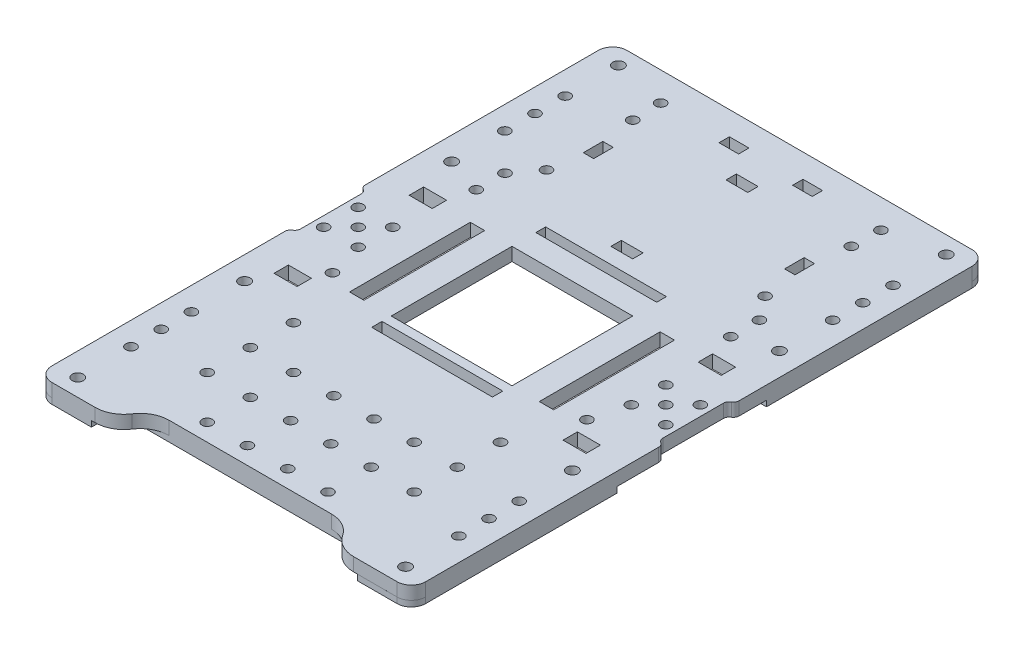
SolidWorks part; units mm, degrees
ref_plane "前视基准面" through (0, 0, 0) normal (0, 0, 1) x (1, 0, 0)
ref_plane "上视基准面" through (0, 0, 0) normal (0, 1, 0) x (1, 0, 0)
ref_plane "右视基准面" through (0, 0, 0) normal (1, 0, 0) x (0, 0, -1)
other "Configuration Table"
sketch "草图2" plane through (0, 0, 0) normal (0, 1, 0) x (1, 0, 0)
  line L0 (-65, 0) -> (65, 0) construction
  line L1 (-65, 100) -> (65, 100)
  line L2 (-65, 100) -> (-65, -100)
  line L3 (-65, -100) -> (65, -100)
  line L4 (65, 100) -> (65, -100)
  line L5 (-65, 100) -> (65, -100) construction
  line L6 (-65, -100) -> (65, 100) construction
  line L7 (65, 0) -> (63, 0) construction
  line L8 (63, 0) -> (59.5, 0) construction
  line L9 (59.5, 0) -> (47.5, 0) construction
  line L10 (47.5, 0) -> (53.5, 0) construction
  line L11 (53.5, 0) -> (53.5, 6) construction
  line L12 (53.5, 6) -> (53.5, -6) construction
  line L13 (53.5, -6) -> (47.5, -6) construction
  line L14 (47.5, -6) -> (47.5, 6) construction
  line L15 (47.5, 6) -> (59.5, 6) construction
  line L16 (59.5, 6) -> (59.5, -6) construction
  line L17 (-65, 0) -> (-63, 0) construction
  line L18 (-63, 0) -> (-59.5, 0) construction
  line L19 (-59.5, 0) -> (-47.5, 0) construction
  line L20 (-47.5, 0) -> (-53.5, 0) construction
  line L21 (-53.5, 0) -> (-53.5, 6) construction
  line L22 (-53.5, 6) -> (-53.5, -6) construction
  line L23 (-53.5, -6) -> (-59.5, -6) construction
  line L24 (-59.5, -6) -> (-59.5, 6) construction
  line L25 (-59.5, 6) -> (-47.5, 6) construction
  line L26 (-47.5, 6) -> (-47.5, -6) construction
  circle A0 centre (-59.5, 6) radius 1.8
  circle A1 centre (-47.5, 6) radius 1.8
  circle A2 centre (-59.5, -6) radius 1.8
  circle A3 centre (-47.5, -6) radius 1.8
  circle A4 centre (-53.5, 0) radius 1.8
  circle A5 centre (53.5, 0) radius 1.8
  circle A6 centre (59.5, 6) radius 1.8
  circle A7 centre (59.5, -6) radius 1.8
  circle A8 centre (47.5, -6) radius 1.8
  circle A9 centre (47.5, 6) radius 1.8
  point P0 (0, 0)
  dimension "D13" = 3.6
  dimension "D14" = 3.6
  dimension "D15" = 3.6
  dimension "D16" = 3.6
  dimension "D17" = 3.6
  dimension "D18" = 3.6
  dimension "D19" = 3.6
  dimension "D20" = 3.6
  dimension "D21" = 3.6
  dimension "D22" = 3.6
  dimension "D1" = 200
  dimension "D2" = 130
  dimension "D3" = 2
  dimension "D4" = 3.5
  dimension "D5" = 12
  dimension "D6" = 6
  dimension "D7" = 12
  dimension "D8" = 2
  dimension "D9" = 3.5
  dimension "D10" = 12
  dimension "D11" = 6
  dimension "D12" = 12
extrude "凸台-拉伸1" add sketch "草图2" along normal blind 4.6
fillet "圆角1" radius 5 4 edges at (-65, 2.3, -100) (65, 2.3, -100) (-65, 2.3, 100) (65, 2.3, 100)
sketch "草图3" plane through (0, 4.6, 0) normal (0, 1, 0) x (1, 0, 0)
  line L0 (-65, 0) -> (65, 0) construction
  line L1 (-65, 95) -> (-65, -95) construction
  line L2 (65, -95) -> (65, 95) construction
  line L4 (-63, 12) -> (-67, 12)
  line L5 (-63, 12) -> (-63, -12)
  line L6 (-63, -12) -> (-67, -12)
  line L7 (-67, 12) -> (-67, -12)
  line L8 (-63, 12) -> (-67, -12) construction
  line L9 (-63, -12) -> (-67, 12) construction
  line L10 (63, 12) -> (67, 12)
  line L11 (63, 12) -> (63, -12)
  line L12 (63, -12) -> (67, -12)
  line L13 (67, 12) -> (67, -12)
  line L14 (63, 12) -> (67, -12) construction
  line L15 (63, -12) -> (67, 12) construction
  dimension "D1" = 24
  dimension "D2" = 4
  dimension "D3" = 24
  dimension "D4" = 4
extrude "切除-拉伸1" cut sketch "草图3" against normal blind 4.6
fillet "圆角2" radius 2 4 edges at (65, 2.3, 12) (65, 2.3, -12) (-65, 2.3, 12) (-65, 2.3, -12)
fillet "圆角3" radius 2 4 edges at (-63, 2.3, 12) (-63, 2.3, -12) (63, 2.3, 12) (63, 2.3, -12)
sketch "草图4" plane through (0, 0, 0) normal (0, 1, 0) x (1, 0, 0)
  line L0 (65, 14) -> (57, 14) construction
  line L1 (57, 14) -> (57, 120) construction
  line L2 (65, -14) -> (57, -14) construction
  line L3 (65, -95) -> (65, -14) construction
  line L4 (57, -14) -> (57, -94) construction
  line L5 (57, -94) -> (57, -65) construction
  line L6 (57, -65) -> (57, -54) construction
  line L7 (-65, -94) -> (-57, -94) construction
  line L8 (-65, -14) -> (-65, -95) construction
  line L9 (-57, -94) -> (-57, -65) construction
  line L10 (-57, -65) -> (-57, -54.5) construction
  line L11 (-57, -54.5) -> (-57, -65) construction
  line L12 (-57, -65) -> (-57, -36) construction
  line L13 (57, -65) -> (57, -36) construction
  line L14 (57, 14) -> (57, 36) construction
  line L15 (57, 36) -> (57, 65) construction
  line L16 (57, 65) -> (57, 75.5) construction
  line L17 (57, 75.5) -> (57, 54.5) construction
  line L18 (57, 65) -> (57, 94) construction
  line L19 (-65, 14) -> (-57, 14) construction
  line L20 (-57, 14) -> (-57, 36) construction
  line L21 (-57, 36) -> (-57, 54.5) construction
  line L22 (-57, 54.5) -> (-57, 65) construction
  line L23 (-57, 65) -> (-57, 75.5) construction
  line L24 (-57, 75.5) -> (-57, 94) construction
  line L25 (-57, -65) -> (-57, -75.5) construction
  line L26 (-57, -75.5) -> (57, -75.5) construction
  line L27 (57, -65) -> (57, -54.5) construction
  arc A0 (65, -14) -> (64, -12.2679) centre (63, -14) ccw construction
  circle A1 centre (57, 65) radius 1.8
  circle A2 centre (57, 75.5) radius 1.8
  circle A3 centre (57, 54.5) radius 1.8
  circle A4 centre (57, 94) radius 1.95
  circle A5 centre (57, 36) radius 1.95
  circle A6 centre (-57, 94) radius 1.95
  circle A7 centre (-57, 75.5) radius 1.8
  circle A8 centre (-57, 65) radius 1.8
  circle A9 centre (-57, 54.5) radius 1.8
  circle A10 centre (-57, 36) radius 1.95
  circle A11 centre (-57, -36) radius 1.95
  circle A12 centre (-57, -65) radius 1.8
  circle A13 centre (-57, -54.5) radius 1.8
  circle A14 centre (-57, -75.5) radius 1.8
  circle A15 centre (-57, -94) radius 1.95
  circle A16 centre (57, -65) radius 1.8
  circle A18 centre (57, -75.5) radius 1.8
  circle A19 centre (57, -54.5) radius 1.8
  circle A20 centre (57, -36) radius 1.95
  circle A21 centre (57, -94) radius 1.95
  dimension "D15" = 3.6
  dimension "D16" = 3.6
  dimension "D17" = 3.6
  dimension "D18" = 3.9
  dimension "D19" = 3.9
  dimension "D20" = 3.9
  dimension "D21" = 3.6
  dimension "D22" = 3.6
  dimension "D23" = 3.6
  dimension "D24" = 3.9
  dimension "D25" = 3.9
  dimension "D26" = 3.6
  dimension "D27" = 3.6
  dimension "D29" = 3.6
  dimension "D30" = 3.9
  dimension "D31" = 3.6
  dimension "D32" = 10.5
  dimension "D33" = 3.6
  dimension "D34" = 3.6
  dimension "D35" = 3.9
  dimension "D36" = 3.9
  dimension "D1" = 8
  dimension "D2" = 106
  dimension "D3" = 8
  dimension "D4" = 80
  dimension "D5" = 29
  dimension "D6" = 11
  dimension "D7" = 8
  dimension "D8" = 29
  dimension "D9" = 22
  dimension "D10" = 29
  dimension "D11" = 10.5
  dimension "D12" = 21
  dimension "D13" = 29
  dimension "D14" = 8
  dimension "D28" = 10.5
extrude "切除-拉伸2" cut sketch "草图4" along normal blind 4.6
sketch "草图5" plane through (0, 4.6, 0) normal (0, 1, 0) x (1, 0, 0)
  line L0 (0, 100) -> (38.3, 100) construction
  line L1 (60, 100) -> (-60, 100) construction
  line L2 (38.3, 100) -> (-38.3, 100) construction
  line L3 (-38.3, 100) -> (-38.3, 90) construction
  line L4 (-38.3, 90) -> (-12.8, 90) construction
  line L5 (38.3, 100) -> (38.3, 90) construction
  line L6 (38.3, 90) -> (12.8, 90) construction
  line L7 (0, 21) -> (0, 31) construction
  line L8 (-16.2, 91.8) -> (-9.4, 91.8)
  line L9 (-16.2, 91.8) -> (-16.2, 88.2)
  line L10 (-16.2, 88.2) -> (-9.4, 88.2)
  line L11 (-9.4, 91.8) -> (-9.4, 88.2)
  line L12 (-16.2, 91.8) -> (-9.4, 88.2) construction
  line L13 (-16.2, 88.2) -> (-9.4, 91.8) construction
  line L14 (9.4, 91.8) -> (16.2, 91.8)
  line L15 (9.4, 91.8) -> (9.4, 88.2)
  line L16 (9.4, 88.2) -> (16.2, 88.2)
  line L17 (16.2, 91.8) -> (16.2, 88.2)
  line L18 (9.4, 91.8) -> (16.2, 88.2) construction
  line L19 (9.4, 88.2) -> (16.2, 91.8) construction
  line L20 (-21, 21) -> (21, 21)
  line L21 (-21, 21) -> (-21, -21)
  line L22 (-21, -21) -> (21, -21)
  line L23 (21, 21) -> (21, -21)
  line L24 (-21, 21) -> (21, -21) construction
  line L25 (-21, -21) -> (21, 21) construction
  line L26 (0, 31) -> (0, -21) construction
  line L27 (0, -21) -> (0, -31) construction
  line L28 (-60, -100) -> (60, -100) construction
  line L29 (-21, 32.7) -> (21, 32.7)
  line L30 (-21, 32.7) -> (-21, 29.3)
  line L31 (-21, 29.3) -> (21, 29.3)
  line L32 (21, 32.7) -> (21, 29.3)
  line L33 (-21, 32.7) -> (21, 29.3) construction
  line L34 (-21, 29.3) -> (21, 32.7) construction
  line L35 (-21, -29.3) -> (21, -29.3)
  line L36 (-21, -29.3) -> (-21, -32.7)
  line L37 (-21, -32.7) -> (21, -32.7)
  line L38 (21, -29.3) -> (21, -32.7)
  line L39 (-21, -29.3) -> (21, -32.7) construction
  line L40 (-21, -32.7) -> (21, -29.3) construction
  line L41 (-35, -91) -> (35, -91)
  line L42 (-35, -91) -> (-35, -109)
  line L43 (-35, -109) -> (35, -109)
  line L44 (35, -91) -> (35, -109)
  line L45 (-35, -91) -> (35, -109) construction
  line L46 (-35, -109) -> (35, -91) construction
  circle A0 centre (38.3, 90) radius 1.8
  circle A1 centre (-38.3, 90) radius 1.8
  point P19 (0, 0)
  point P37 (0, -100)
  dimension "D7" = 3.6
  dimension "D8" = 3.6
  dimension "D1" = 38.3
  dimension "D2" = 76.6
  dimension "D3" = 10
  dimension "D4" = 25.5
  dimension "D5" = 10
  dimension "D6" = 25.5
  dimension "D9" = 3.6
  dimension "D10" = 6.8
  dimension "D11" = 3.6
  dimension "D12" = 6.8
  dimension "D13" = 42
  dimension "D14" = 10
  dimension "D15" = 10
  dimension "D16" = 3.4
  dimension "D17" = 42
  dimension "D18" = 3.4
  dimension "D19" = 42
  dimension "D20" = 18
  dimension "D21" = 70
extrude "切除-拉伸3" cut sketch "草图5" against normal blind 4.6
fillet "圆角4" radius 10 2 edges at (-35, 2.3, 100) (35, 2.3, 100)
fillet "圆角5" radius 10 2 edges at (-35, 2.3, 91) (35, 2.3, 91)
sketch "草图6" plane through (0, 4.6, 0) normal (0, 1, 0) x (1, 0, 0)
  line L0 (0, -91) -> (0, -85) construction
  line L1 (28.2466, -91) -> (-28.2466, -91) construction
  line L2 (0, -85) -> (-7, -85) construction
  line L3 (-7, -85) -> (7, -85) construction
  line L4 (7, -85) -> (21, -85) construction
  line L5 (21, -85) -> (21, -70) construction
  line L6 (21, -70) -> (21, -55) construction
  line L7 (21, -55) -> (7, -55) construction
  line L8 (7, -55) -> (-7, -55) construction
  line L9 (-7, -55) -> (-21, -55) construction
  line L10 (-21, -55) -> (-35, -55) construction
  line L11 (-35, -55) -> (-35, -70) construction
  line L12 (-35, -70) -> (-35, -85) construction
  line L13 (-35, -85) -> (-21, -85) construction
  line L14 (21, -85) -> (35, -85) construction
  line L15 (35, -85) -> (35, -70) construction
  line L16 (35, -70) -> (35, -55) construction
  line L17 (35, -55) -> (35, -40) construction
  line L18 (35, -40) -> (21, -40) construction
  line L19 (21, -40) -> (7, -40) construction
  line L20 (7, -40) -> (-7, -40) construction
  line L21 (-7, -40) -> (-21, -40) construction
  line L22 (-21, -40) -> (-35, -40) construction
  line L23 (-35, -40) -> (-35, -70) construction
  line L24 (-35, -70) -> (-21, -70) construction
  line L25 (-21, -70) -> (-7, -70) construction
  line L26 (-7, -70) -> (7, -70) construction
  line L27 (21, -70) -> (36, -70) construction
  line L28 (36, -70) -> (36, -55) construction
  line L29 (36, -55) -> (36, -40) construction
  line L30 (-21, -70) -> (-36, -70) construction
  line L31 (-36, -70) -> (-36, -55) construction
  line L32 (-36, -55) -> (-36, -40) construction
  circle A0 centre (-7, -85) radius 1.8
  circle A1 centre (-21, -85) radius 1.8
  circle A2 centre (7, -85) radius 1.8
  circle A3 centre (21, -85) radius 1.8
  circle A4 centre (21, -70) radius 1.8
  circle A5 centre (7, -70) radius 1.8
  circle A6 centre (-7, -70) radius 1.8
  circle A7 centre (-21, -70) radius 1.8
  circle A8 centre (-21, -55) radius 1.8
  circle A9 centre (-7, -55) radius 1.8
  circle A10 centre (7, -55) radius 1.8
  circle A11 centre (21, -55) radius 1.8
  circle A12 centre (36, -70) radius 1.8
  circle A13 centre (36, -55) radius 1.8
  circle A14 centre (36, -40) radius 1.8
  circle A15 centre (-36, -40) radius 1.8
  circle A16 centre (-36, -55) radius 1.8
  circle A17 centre (-36, -70) radius 1.8
  dimension "D15" = 3.6
  dimension "D16" = 3.6
  dimension "D17" = 3.6
  dimension "D18" = 3.6
  dimension "D19" = 3.6
  dimension "D20" = 3.6
  dimension "D21" = 3.6
  dimension "D22" = 3.6
  dimension "D23" = 3.6
  dimension "D24" = 3.6
  dimension "D25" = 3.6
  dimension "D26" = 3.6
  dimension "D27" = 15
  dimension "D33" = 3.6
  dimension "D34" = 3.6
  dimension "D35" = 3.6
  dimension "D36" = 3.6
  dimension "D37" = 3.6
  dimension "D38" = 3.6
  dimension "D1" = 6
  dimension "D2" = 7
  dimension "D3" = 14
  dimension "D4" = 14
  dimension "D5" = 15
  dimension "D6" = 15
  dimension "D7" = 14
  dimension "D8" = 14
  dimension "D9" = 14
  dimension "D10" = 14
  dimension "D11" = 15
  dimension "D12" = 14
  dimension "D13" = 14
  dimension "D14" = 15
  dimension "D28" = 15
  dimension "D29" = 15
  dimension "D30" = 15
  dimension "D31" = 15
  dimension "D32" = 15
extrude "切除-拉伸4" cut sketch "草图6" against normal blind 4.6
sketch "草图7" plane through (0, 4.6, 0) normal (0, 1, 0) x (1, 0, 0)
  line L0 (0, 100) -> (38, 100) construction
  line L1 (60, 100) -> (-60, 100) construction
  line L2 (38, 100) -> (-38, 100) construction
  line L3 (-38, 100) -> (-38, 80) construction
  line L4 (-38, 80) -> (-38, 50) construction
  line L5 (-38, 50) -> (38, 50) construction
  line L6 (38, 50) -> (38, 80) construction
  circle A0 centre (-38, 80) radius 1.8
  circle A1 centre (38, 80) radius 1.8
  circle A2 centre (38, 50) radius 1.8
  circle A3 centre (-38, 50) radius 1.8
  dimension "D7" = 3.6
  dimension "D8" = 3.6
  dimension "D9" = 3.6
  dimension "D10" = 3.6
  dimension "D1" = 38
  dimension "D2" = 76
  dimension "D3" = 20
  dimension "D4" = 30
  dimension "D5" = 76
  dimension "D6" = 30
extrude "切除-拉伸5" cut sketch "草图7" against normal blind 4.6
sketch "草图8" plane through (0, 4.6, 0) normal (0, 1, 0) x (1, 0, 0)
  line L0 (-38, 80) -> (38, 50) construction
  line L1 (38, 50) -> (0, 65) construction
  line L2 (0, 65) -> (-35, 65) construction
  line L3 (-35, 65) -> (35, 65) construction
  line L4 (35, 65) -> (0, 65) construction
  line L5 (0, 65) -> (0, 80) construction
  line L6 (0, 80) -> (0, 40) construction
  line L8 (-3.7805, 81.7985) -> (3.7805, 81.7985)
  line L9 (-3.7805, 81.7985) -> (-3.7805, 78.2015)
  line L10 (-3.7805, 78.2015) -> (3.7805, 78.2015)
  line L11 (3.7805, 81.7985) -> (3.7805, 78.2015)
  line L12 (-3.7805, 81.7985) -> (3.7805, 78.2015) construction
  line L13 (-3.7805, 78.2015) -> (3.7805, 81.7985) construction
  line L14 (-3.7805, 38.1892) -> (3.7805, 38.1892)
  line L15 (-3.7805, 38.1892) -> (-3.7805, 41.8108)
  line L16 (-3.7805, 41.8108) -> (3.7805, 41.8108)
  line L17 (3.7805, 38.1892) -> (3.7805, 41.8108)
  line L18 (-3.7805, 38.1892) -> (3.7805, 41.8108) construction
  line L19 (-3.7805, 41.8108) -> (3.7805, 38.1892) construction
  line L20 (33.2, 68.4) -> (36.8, 68.4)
  line L21 (33.2, 68.4) -> (33.2, 61.6)
  line L22 (33.2, 61.6) -> (36.8, 61.6)
  line L23 (36.8, 68.4) -> (36.8, 61.6)
  line L24 (33.2, 68.4) -> (36.8, 61.6) construction
  line L25 (33.2, 61.6) -> (36.8, 68.4) construction
  line L26 (-36.8, 68.4) -> (-33.2, 68.4)
  line L27 (-36.8, 68.4) -> (-36.8, 61.6)
  line L28 (-36.8, 61.6) -> (-33.2, 61.6)
  line L29 (-33.2, 68.4) -> (-33.2, 61.6)
  line L30 (-36.8, 68.4) -> (-33.2, 61.6) construction
  line L31 (-36.8, 61.6) -> (-33.2, 68.4) construction
  dimension "D1" = 35
  dimension "D2" = 70
  dimension "D3" = 40
  dimension "D4" = 6.8
  dimension "D5" = 3.6
  dimension "D6" = 6.8
  dimension "D7" = 3.6
extrude "切除-拉伸6" cut sketch "草图8" against normal blind 4.6
sketch "草图10" plane through (0, 4.6, 0) normal (0, 1, 0) x (1, 0, 0)
  line L0 (0, 0) -> (44.25, 0) construction
  line L1 (44.25, 0) -> (-44.25, 0) construction
  line L2 (36, -38.2) -> (73.5514, -38.2) construction
  line L3 (73.5514, -38.2) -> (-76.1567, -38.2) construction
  line L4 (44.25, 0) -> (44.25, -38.2) construction
  line L5 (44.25, -38.2) -> (44.25, -18.2) construction
  line L6 (-44.25, 0) -> (-44.25, -38.2) construction
  line L7 (-44.25, -38.2) -> (-44.25, -18.1899) construction
  line L8 (-44.25, -18.1899) -> (-43.1477, 41.8) construction
  line L9 (-43.1477, 41.8) -> (44.25, 41.8) construction
  line L10 (0, 38.1892) -> (-44.25, 38.1892) construction
  line L11 (-3.7805, 38.1892) -> (3.7805, 38.1892) construction
  line L12 (-44.25, 38.1892) -> (44.25, 38.1892) construction
  line L13 (-44.25, -18.1899) -> (-44.25, 41.8101) construction
  line L14 (44.25, -18.2) -> (44.25, 41.8) construction
  line L15 (44.25, -18.2) -> (44.25, -8.2) construction
  line L16 (-44.25, -18.1899) -> (-44.25, -8.1899) construction
  line L17 (-44.25, -18.1899) -> (-44.25, 31.8101) construction
  line L18 (-44.25, 31.8101) -> (44.25, 31.8101) construction
  circle A0 centre (36, -40) radius 1.8 construction
  circle A1 centre (44.25, 41.8) radius 1.8
  circle A2 centre (-44.25, 41.8101) radius 1.8
  circle A3 centre (-44.25, -18.1899) radius 1.8
  circle A4 centre (44.25, -18.2) radius 1.8
  circle A5 centre (-44.25, 31.8101) radius 1.8
  circle A6 centre (44.25, 31.8101) radius 1.8
  dimension "D9" = 3.6
  dimension "D10" = 3.6
  dimension "D11" = 3.6
  dimension "D12" = 3.6
  dimension "D16" = 3.6
  dimension "D17" = 3.6
  dimension "D1" = 44.25
  dimension "D2" = 88.5
  dimension "D3" = 20
  dimension "D4" = 60
  dimension "D5" = 44.25
  dimension "D6" = 88.5
  dimension "D7" = 60
  dimension "D8" = 60
  dimension "D13" = 10
  dimension "D14" = 10
  dimension "D15" = 50
extrude "切除-拉伸8" cut sketch "草图10" against normal blind 4.6
sketch "草图9" plane through (0, 4.6, 0) normal (0, 1, 0) x (1, 0, 0)
  line L0 (21, 0) -> (33, 0) construction
  line L1 (21, -21) -> (21, 21) construction
  line L2 (-21, 0) -> (-33, 0) construction
  line L3 (-21, 21) -> (-21, -21) construction
  line L4 (35.5, -21) -> (65, -21) construction
  line L9 (30.5, 21) -> (35.5, -21) construction
  line L10 (30.5, -21) -> (35.5, 21) construction
  line L15 (-35.5, 21) -> (-30.5, -21) construction
  line L16 (-35.5, -21) -> (-30.5, 21) construction
  line L17 (65, -95) -> (65, -14) construction
  line L18 (-35.5, -21) -> (-65, -21) construction
  line L23 (46.25, -18.5) -> (54.25, -23.5) construction
  line L24 (46.25, -23.5) -> (54.25, -18.5) construction
  line L25 (-65, -14) -> (-65, -95) construction
  line L26 (-35.5, 21) -> (-65, 21) construction
  line L31 (-54.25, -18.5) -> (-46.25, -23.5) construction
  line L32 (-54.25, -23.5) -> (-46.25, -18.5) construction
  line L33 (-65, 95) -> (-65, 14) construction
  line L34 (35.5, 21) -> (65, 21) construction
  line L35 (-54.25, 23.5) -> (-46.25, 23.5)
  line L36 (-54.25, 23.5) -> (-54.25, 18.5)
  line L37 (-54.25, 18.5) -> (-46.25, 18.5)
  line L38 (-46.25, 23.5) -> (-46.25, 18.5)
  line L39 (-54.25, 23.5) -> (-46.25, 18.5) construction
  line L40 (-54.25, 18.5) -> (-46.25, 23.5) construction
  line L41 (65, 14) -> (65, 95) construction
  line L42 (50.25, -21) -> (50.25, -31) construction
  line L43 (46.25, 23.5) -> (54.25, 23.5)
  line L44 (46.25, 23.5) -> (46.25, 18.5)
  line L45 (46.25, 18.5) -> (54.25, 18.5)
  line L46 (54.25, 23.5) -> (54.25, 18.5)
  line L47 (46.25, 23.5) -> (54.25, 18.5) construction
  line L48 (46.25, 18.5) -> (54.25, 23.5) construction
  line L49 (50.25, -31) -> (50.25, -26) construction
  line L50 (50.25, -26) -> (-50.25, -26) construction
  line L52 (-54.25, -23.5) -> (-46.25, -23.5)
  line L53 (-54.25, -23.5) -> (-54.25, -28.5)
  line L54 (-54.25, -28.5) -> (-46.25, -28.5)
  line L55 (-46.25, -23.5) -> (-46.25, -28.5)
  line L56 (-54.25, -23.5) -> (-46.25, -28.5) construction
  line L57 (-54.25, -28.5) -> (-46.25, -23.5) construction
  line L58 (46.25, -23.5) -> (54.25, -23.5)
  line L59 (46.25, -23.5) -> (46.25, -28.5)
  line L60 (46.25, -28.5) -> (54.25, -28.5)
  line L61 (54.25, -23.5) -> (54.25, -28.5)
  line L62 (46.25, -23.5) -> (54.25, -28.5) construction
  line L63 (46.25, -28.5) -> (54.25, -23.5) construction
  line L64 (30.5, 21) -> (35.5, 21)
  line L65 (30.5, 21) -> (30.5, -21)
  line L66 (30.5, -21) -> (35.5, -21)
  line L67 (35.5, 21) -> (35.5, -21)
  line L68 (30.5, 21) -> (35.5, -21) construction
  line L69 (30.5, -21) -> (35.5, 21) construction
  line L70 (-35.5, 21) -> (-30.5, 21)
  line L71 (-35.5, 21) -> (-35.5, -21)
  line L72 (-35.5, -21) -> (-30.5, -21)
  line L73 (-30.5, 21) -> (-30.5, -21)
  line L74 (-35.5, 21) -> (-30.5, -21) construction
  line L75 (-35.5, -21) -> (-30.5, 21) construction
  point P17 (50.25, -21)
  point P25 (-50.25, -21)
  point P33 (-50.25, 21)
  point P41 (50.25, 21)
  dimension "D1" = 12
  dimension "D2" = 12
  dimension "D3" = 42
  dimension "D4" = 5
  dimension "D5" = 42
  dimension "D6" = 5
  dimension "D7" = 5
  dimension "D8" = 8
  dimension "D9" = 5
  dimension "D10" = 8
  dimension "D11" = 5
  dimension "D12" = 8
  dimension "D13" = 5
  dimension "D14" = 8
  dimension "D15" = 10
  dimension "D16" = 5
  dimension "D17" = 8
  dimension "D18" = 5
  dimension "D19" = 8
extrude "切除-拉伸9" cut sketch "草图9" against normal blind 4.6
sketch "草图12" plane through (0, 0, 0) normal (0, -1, 0) x (1, 0, 0)
  line L0 (-46.25, 28.5) -> (-46.25, 23.5) construction
  line L1 (-65, 100) -> (-46.25, 100)
  line L2 (-65, 100) -> (-65, 28.5)
  line L3 (-65, 28.5) -> (-46.25, 28.5)
  line L4 (-46.25, 100) -> (-46.25, 28.5)
  line L5 (-54.25, 28.5) -> (-46.25, 28.5) construction
  line L6 (65, 95) -> (65, 100.0021) construction
  line L7 (-60, -100) -> (-65, -100) construction
  line L8 (65, 100.0021) -> (46.25, 100.0021)
  line L9 (65, 100.0021) -> (65, 28.5)
  line L10 (65, 28.5) -> (46.25, 28.5)
  line L11 (46.25, 100.0021) -> (46.25, 28.5)
  line L12 (-46.25, -23.5) -> (-54.25, -23.5) construction
  line L13 (-65, -100) -> (-50.25, -100)
  line L14 (-65, -100) -> (-65, -23.5)
  line L15 (-65, -23.5) -> (-50.25, -23.5)
  line L16 (-50.25, -100) -> (-50.25, -23.5)
  line L17 (54.25, -23.5) -> (46.25, -23.5) construction
  line L18 (65, -99.9979) -> (50.25, -99.9979)
  line L19 (65, -99.9979) -> (65, -23.5)
  line L20 (65, -23.5) -> (50.25, -23.5)
  line L21 (50.25, -99.9979) -> (50.25, -23.5)
  line L22 (-50.25, -55.9334) -> (50.25, -55.9334) construction
  line L23 (50.25, -55.9334) -> (50.25, -72.845) construction
  line L24 (50.25, -72.845) -> (-50.25, -72.845) construction
  line L25 (-21, 85) -> (-21, 70) construction
  line L26 (-21, 70) -> (-21, 77.5) construction
  line L27 (-21, 77.5) -> (-46.25, 77.5) construction
  line L28 (-46.25, 77.5) -> (46.25, 77.5) construction
  line L29 (46.25, 77.5) -> (0, 77.5) construction
  line L30 (0, 77.5) -> (0, 62.5) construction
  line L31 (0, 62.5) -> (0, 47.5) construction
  line L32 (0, 77.5) -> (0, 92.5) construction
  line L33 (-28.2466, 91) -> (-46.25, 91) construction
  line L34 (-46.25, 91) -> (46.25, 91) construction
  line L35 (-21, 32.7) -> (-46.25, 32.7) construction
  line L36 (-46.25, 79.5003) -> (46.25, 79.5003)
  line L37 (-46.25, 79.5003) -> (-46.25, 75.4997)
  line L38 (-46.25, 75.4997) -> (46.25, 75.4997)
  line L39 (46.25, 79.5003) -> (46.25, 75.4997)
  line L40 (-46.25, 79.5003) -> (46.25, 75.4997) construction
  line L41 (-46.25, 75.4997) -> (46.25, 79.5003) construction
  line L42 (-46.25, 64.5) -> (46.25, 64.5)
  line L43 (-46.25, 64.5) -> (-46.25, 60.5)
  line L44 (-46.25, 60.5) -> (46.25, 60.5)
  line L45 (46.25, 64.5) -> (46.25, 60.5)
  line L46 (-46.25, 64.5) -> (46.25, 60.5) construction
  line L47 (-46.25, 60.5) -> (46.25, 64.5) construction
  line L48 (-46.25, 49.5) -> (46.25, 49.5)
  line L49 (-46.25, 49.5) -> (-46.25, 45.5)
  line L50 (-46.25, 45.5) -> (46.25, 45.5)
  line L51 (46.25, 49.5) -> (46.25, 45.5)
  line L52 (-46.25, 49.5) -> (46.25, 45.5) construction
  line L53 (-46.25, 45.5) -> (46.25, 49.5) construction
  line L54 (-46.25, 91) -> (46.25, 91)
  line L55 (-46.25, 91) -> (-46.25, 89)
  line L56 (-46.25, 89) -> (46.25, 89)
  line L57 (46.25, 91) -> (46.25, 89)
  line L58 (-46.25, 32.7) -> (46.25, 32.7) construction
  line L59 (0, -55.9334) -> (0, -57.8166) construction
  line L60 (-46.25, 32.7) -> (46.25, 32.7)
  line L61 (-46.25, 32.7) -> (-46.25, 34.7)
  line L62 (-46.25, 34.7) -> (46.25, 34.7)
  line L63 (46.25, 32.7) -> (46.25, 34.7)
  line L64 (-38, -81.8) -> (-38, -88.2252) construction
  line L65 (-50.25, -54.875) -> (50.25, -54.875)
  line L66 (-50.25, -54.875) -> (-50.25, -58.875)
  line L67 (-50.25, -58.875) -> (50.25, -58.875)
  line L68 (50.25, -54.875) -> (50.25, -58.875)
  line L69 (-50.25, -54.875) -> (50.25, -58.875) construction
  line L70 (-50.25, -58.875) -> (50.25, -54.875) construction
  line L71 (-50.25, -74.845) -> (50.25, -74.845)
  line L72 (-50.25, -74.845) -> (-50.25, -70.845)
  line L73 (-50.25, -70.845) -> (50.25, -70.845)
  line L74 (50.25, -74.845) -> (50.25, -70.845)
  line L75 (-50.25, -74.845) -> (50.25, -70.845) construction
  line L76 (-50.25, -70.845) -> (50.25, -74.845) construction
  line L77 (-38, -85.0126) -> (67.8048, -85.0126) construction
  line L78 (0, -81.7985) -> (0, -85.0126) construction
  line L79 (3.7805, -81.7985) -> (-3.7805, -81.7985) construction
  line L80 (0, -85.0126) -> (0, -95.8032) construction
  line L81 (-50.25, -84.0126) -> (50.25, -84.0126)
  line L82 (-50.25, -84.0126) -> (-50.25, -86.0126)
  line L83 (-50.25, -86.0126) -> (50.25, -86.0126)
  line L84 (50.25, -84.0126) -> (50.25, -86.0126)
  line L85 (-50.25, -84.0126) -> (50.25, -86.0126) construction
  line L86 (-50.25, -86.0126) -> (50.25, -84.0126) construction
  line L87 (0, -56.875) -> (0, -72.845) construction
  line L88 (-50.25, -94.3032) -> (50.25, -94.3032)
  line L89 (-50.25, -94.3032) -> (-50.25, -97.3032)
  line L90 (-50.25, -97.3032) -> (50.25, -97.3032)
  line L91 (50.25, -94.3032) -> (50.25, -97.3032)
  line L92 (-50.25, -94.3032) -> (50.25, -97.3032) construction
  line L93 (-50.25, -97.3032) -> (50.25, -94.3032) construction
  line L94 (3.7805, -80) -> (36.2, -80) construction
  line L95 (-2, -58.875) -> (2, -58.875)
  line L96 (-2, -58.875) -> (-2, -70.845)
  line L97 (-2, -70.845) -> (2, -70.845)
  line L98 (2, -58.875) -> (2, -70.845)
  line L99 (-2, -58.875) -> (2, -70.845) construction
  line L100 (-2, -70.845) -> (2, -58.875) construction
  line L101 (3.7805, -78.2015) -> (3.7805, -81.7985) construction
  line L102 (-3.7805, -80) -> (-36.2, -80) construction
  line L103 (-3.7805, -81.7985) -> (-3.7805, -78.2015) construction
  line L104 (22.8, 55) -> (34.2, 55) construction
  line L105 (17.9902, -85.155) -> (21.9902, -85.155)
  line L106 (17.9902, -85.155) -> (17.9902, -74.845)
  line L107 (17.9902, -74.845) -> (21.9902, -74.845)
  line L108 (21.9902, -85.155) -> (21.9902, -74.845)
  line L109 (17.9902, -85.155) -> (21.9902, -74.845) construction
  line L110 (17.9902, -74.845) -> (21.9902, -85.155) construction
  line L111 (-21.9902, -85.845) -> (-17.9902, -85.845)
  line L112 (-21.9902, -85.845) -> (-21.9902, -74.155)
  line L113 (-21.9902, -74.155) -> (-17.9902, -74.155)
  line L114 (-17.9902, -85.845) -> (-17.9902, -74.155)
  line L115 (-21.9902, -85.845) -> (-17.9902, -74.155) construction
  line L116 (-21.9902, -74.155) -> (-17.9902, -85.845) construction
  line L117 (-2, -84.9529) -> (2, -84.9529)
  line L118 (-2, -84.9529) -> (-2, -95.8629)
  line L119 (-2, -95.8629) -> (2, -95.8629)
  line L120 (2, -84.9529) -> (2, -95.8629)
  line L121 (-2, -84.9529) -> (2, -95.8629) construction
  line L122 (-2, -95.8629) -> (2, -84.9529) construction
  line L123 (-2, 49) -> (2, 49)
  line L124 (-2, 49) -> (-2, 91)
  line L125 (-2, 91) -> (2, 91)
  line L126 (2, 49) -> (2, 91)
  line L127 (-2, 49) -> (2, 91) construction
  line L128 (-2, 91) -> (2, 49) construction
  line L129 (-34.2, 55) -> (-22.8, 55) construction
  line L131 (26.5, 75.3) -> (30.5, 75.3)
  line L132 (26.5, 75.3) -> (26.5, 34.7)
  line L133 (26.5, 34.7) -> (30.5, 34.7)
  line L134 (30.5, 75.3) -> (30.5, 34.7)
  line L135 (26.5, 75.3) -> (30.5, 34.7) construction
  line L136 (26.5, 34.7) -> (30.5, 75.3) construction
  line L137 (-30.5, 75.3) -> (-26.5, 75.3)
  line L138 (-30.5, 75.3) -> (-30.5, 34.7)
  line L139 (-30.5, 34.7) -> (-26.5, 34.7)
  line L140 (-26.5, 75.3) -> (-26.5, 34.7)
  line L141 (-30.5, 75.3) -> (-26.5, 34.7) construction
  line L142 (-30.5, 34.7) -> (-26.5, 75.3) construction
  circle A0 centre (-57, 94) radius 1.95
  circle A1 centre (-57, 75.5) radius 1.8
  circle A2 centre (-57, 65) radius 1.8143
  circle A3 centre (-57, 54.5) radius 1.8
  circle A4 centre (-57, 36) radius 1.95
  circle A5 centre (57, 94) radius 1.95
  circle A6 centre (57, 75.5) radius 1.8
  circle A7 centre (57, 65) radius 1.8
  circle A8 centre (57, 54.5) radius 1.8
  circle A9 centre (57, 36) radius 1.95
  circle A10 centre (57, -36) radius 1.95
  circle A11 centre (57, -54.5) radius 1.8
  circle A12 centre (57, -65) radius 1.8
  circle A13 centre (57, -75.5) radius 1.8
  circle A14 centre (57, -94) radius 1.95
  circle A15 centre (-57, -94) radius 1.95
  circle A16 centre (-57, -75.5) radius 1.8
  circle A17 centre (-57, -65) radius 1.8
  circle A18 centre (-57, -54.5) radius 1.8
  circle A19 centre (-57, -36) radius 1.95
  circle A20 centre (-38, -80) radius 1.8 construction
  circle A21 centre (-38.3, -90) radius 1.8 construction
  circle A22 centre (38, -80) radius 1.8 construction
  circle A23 centre (21, 55) radius 1.8 construction
  circle A24 centre (36, 55) radius 1.8 construction
  circle A25 centre (-36, 55) radius 1.8 construction
  circle A26 centre (-21, 55) radius 1.8 construction
  point P133 (0, -56.875)
  point P138 (0, -72.845)
  point P167 (0, -64.86)
  point P183 (19.9902, -80)
  point P188 (-19.9902, -80)
  point P193 (0, -90.4079)
  point P198 (0, 70)
  point P217 (28.5, 55)
  point P222 (-28.5, 55)
  dimension "D1" = 15
  dimension "D2" = 15
  dimension "D3" = 15
  dimension "D4" = 4.0007
  dimension "D5" = 92.5
  dimension "D6" = 4
  dimension "D7" = 4
  dimension "D8" = 2
  dimension "D9" = 2
  dimension "D10" = 4
  dimension "D11" = 4
  dimension "D12" = 2
  dimension "D13" = 3
  dimension "D14" = 11.97
  dimension "D15" = 4
  dimension "D16" = 10.31
  dimension "D17" = 4
  dimension "D18" = 11.69
  dimension "D19" = 4
  dimension "D20" = 10.91
  dimension "D21" = 4
  dimension "D22" = 42
  dimension "D23" = 4
  dimension "D24" = 40.6
  dimension "D25" = 4
  dimension "D26" = 40.6
  dimension "D27" = 4
extrude "凸台-拉伸2" add sketch "草图12" along normal blind 2 contours L4 L1 L2 L3 A4 A3 A2 A1 A0 | L56 L126 L54 L124 | L126 L56 L11 L54 | L56 L124 L54 L4 | L36 L126 L56 L124 | L8 L11 L10 L9 A9 A8 A7 A6 A5 | L126 L38 L11 L36 | L38 L126 L36 L124 | L38 L124 L36 L4 | L42 L126 L38 L124 | L134 L131 L132 L42 | L140 L137 L138 L42 | L138 L42 L4 L44 | L140 L42 L138 L44 | L42 L140 L44 L124 | L44 L126 L42 L124 | L132 L42 L126 L44 | L134 L42 L132 L44 | L42 L134 L44 L11 | L134 L44 L132 L48 | L48 L134 L50 L11 | L134 L50 L132 L62 | L62 L4 L60 L11 | L134 L48 L132 L50 | L48 L140 L50 L132 L126 L123 L124 | L48 L126 L44 L124 | L123 L126 L48 L124 | L140 L44 L138 L48 | L138 L48 L4 L50 | L140 L48 L138 L50 | L140 L50 L138 L62 | L21 L18 L19 L20 A14 A13 A12 A11 A10 | L13 L16 L15 L14 A19 A18 A17 A16 A15 | L16 L67 L21 L65 | L98 L67 L96 L73 | L114 L71 L21 L73 L16 L112 L113 | L81 L108 L71 L106 | L81 L114 L71 L112 | L71 L114 L113 L112 | L117 L120 L83 L21 L81 L108 L105 L106 L114 L111 L112 L16 L118 | L111 L114 L81 L112 | L105 L108 L81 L106 | L120 L117 L118 L83 | L120 L83 L118 L88 | L88 L120 L119 L118 L16 L90 L21 | L120 L88 L118 L119 region at (-55.625, 0, 99.2608) region at (-24.125, 0, 90) region at (0, 0, 90) region at (0, 0, 33.7) region at (-24.125, 0, 77.5) region at (0, 0, 84.2502) region at (24.125, 0, 90) region at (46.9892, 0, 33.7) region at (0, 0, 77.5) region at (-38.375, 0, 47.5) region at (-28.5, 0, 40.1) region at (-38.375, 0, 62.5) region at (0, 0, 69.9998) region at (24.125, 0, 77.5) region at (-28.5, 0, 47.5) region at (38.375, 0, 47.5) region at (28.5, 0, 40.1) region at (-28.5, 0, 69.9) region at (-28.5, 0, 62.5) region at (-14.25, 0, 62.5) region at (0, 0, 62.5) region at (-28.5, 0, 55) region at (0, 0, 47.4833) region at (28.5, 0, 47.5) region at (14.25, 0, 62.5) region at (0, 0, 55) region at (38.375, 0, 62.5) region at (28.5, 0, 55) region at (28.5, 0, 69.9) region at (28.5, 0, 62.5) region at (0, 0, 49.25) region at (-57.6567, 0, -61.5853) region at (-49.2446, 0, -95.8032) region at (57.6567, 0, -61.5842) region at (0, 0, -56.875) region at (-49.2448, 0, -85.0126) region at (0, 0, -90.1579) region at (0, 0, -95.083) region at (0, 0, -85.4827) region at (0.1382, 0, -72.8336) region at (0, 0, -64.86) region at (-19.9902, 0, -79.4288) region at (-19.9902, 0, -84.9288) region at (-19.9902, 0, -74.5) region at (19.9902, 0, -84.5838) region at (19.9902, 0, -79.4288)
sketch "草图13" plane through (0, 0, 0) normal (0, -1, 0) x (1, 0, 0)
  line L0 (0, -41.8108) -> (0, -45.8108) construction
  line L1 (3.7805, -41.8108) -> (-3.7805, -41.8108) construction
  line L3 (-15, -45.8108) -> (15, -45.8108)
  line L4 (-15, -45.8108) -> (-15, -41.8108)
  line L5 (-15, -41.8108) -> (15, -41.8108)
  line L6 (15, -45.8108) -> (15, -41.8108)
  line L7 (-15, -45.8108) -> (15, -41.8108) construction
  line L8 (-15, -41.8108) -> (15, -45.8108) construction
  point P5 (0, -43.8108)
  dimension "D1" = 4
  dimension "D2" = 4
  dimension "D3" = 30
extrude "凸台-拉伸3" add sketch "草图13" along normal blind 2
fillet "圆角6" radius 5 4 edges at (-65, -1, 100) (65, -1, 100.0021) (-65, -1, -100) (65, -1, -99.9979)
sketch "草图14" plane through (0, 4.6, 0) normal (0, 1, 0) x (1, 0, 0)
  line L1 (21, -32.7) -> (-21, -32.7)
  line L2 (21, -32.7) -> (21, -29.3)
  line L3 (21, -29.3) -> (-21, -29.3)
  line L4 (-21, -32.7) -> (-21, -29.3)
extrude "凸台-拉伸4" add sketch "草图14" against normal up to surface (4.6 mm away) up to face at (0, 0, 1.9679)
sketch "草图15" plane through (0, 4.6, 0) normal (0, 1, 0) x (1, 0, 0)
  line L0 (0, -21) -> (0, -26) construction
  line L1 (-21, -21) -> (21, -21) construction
  line L3 (-21, -24.2) -> (21, -24.2)
  line L4 (-21, -24.2) -> (-21, -27.8)
  line L5 (-21, -27.8) -> (21, -27.8)
  line L6 (21, -24.2) -> (21, -27.8)
  line L7 (-21, -24.2) -> (21, -27.8) construction
  line L8 (-21, -27.8) -> (21, -24.2) construction
  dimension "D1" = 5
  dimension "D2" = 3.6
  dimension "D3" = 42
extrude "切除-拉伸10" cut sketch "草图15" against normal blind 10
